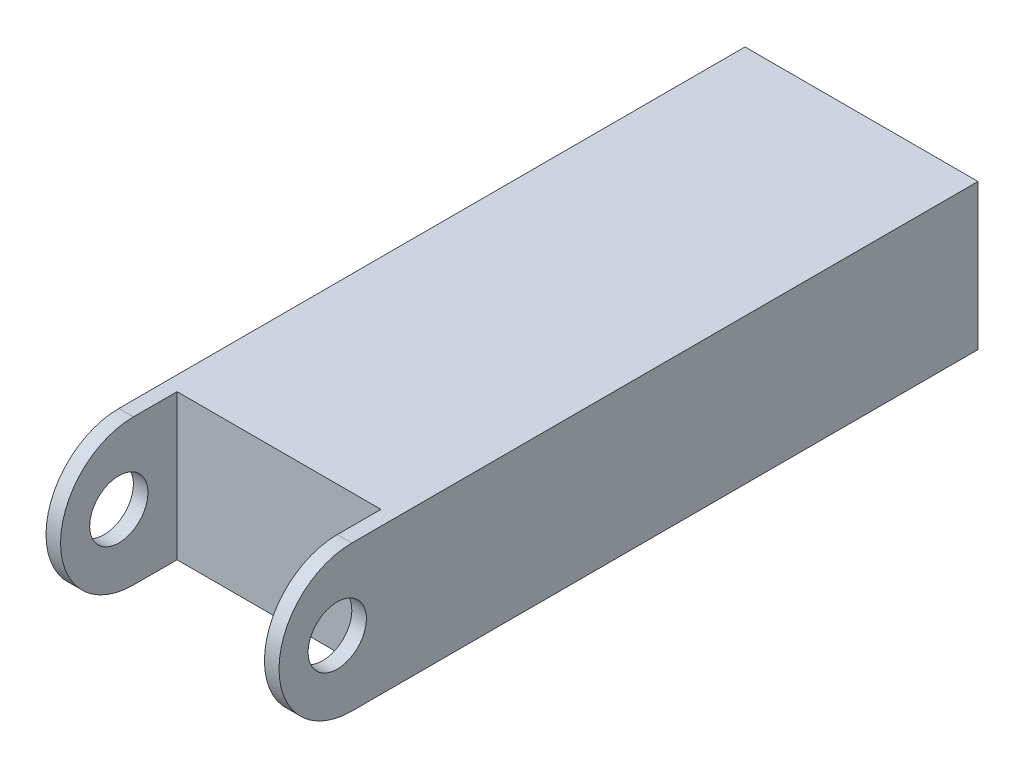
SolidWorks part; units mm, degrees
material "Mahogany"
ref_plane "Front Plane" through (0, 0, 0) normal (0, 0, 1) x (1, 0, 0)
ref_plane "Top Plane" through (0, 0, 0) normal (0, 1, 0) x (1, 0, 0)
ref_plane "Right Plane" through (0, 0, 0) normal (1, 0, 0) x (0, 0, -1)
sketch "Sketch1" plane through (0, 0, 0) normal (0, 0, 1) x (1, 0, 0)
  line L1 (-40, 25) -> (40, 25)
  line L2 (-40, 25) -> (-40, -25)
  line L3 (-40, -25) -> (40, -25)
  line L4 (40, 25) -> (40, -25)
  line L5 (-40, 25) -> (40, -25) construction
  line L6 (-40, -25) -> (40, 25) construction
  point P0 (0, 0)
  dimension "D1" = 80
  dimension "D2" = 50
extrude "Boss-Extrude1" add sketch "Sketch1" against normal blind 200
ref_plane "Plane1" through (0, 0, -200) normal (0, 0, -1) x (-1, 0, 0)
ref_plane "Plane2" through (40, 0, 0) normal (1, 0, 0) x (0, 0, -1)
sketch "Sketch4" plane through (40, 0, 0) normal (1, 0, 0) x (0, 0, -1)
  line L0 (0, 25) -> (0, -25)
  line L1 (0, -25) -> (-40, -25)
  line L2 (-40, -25) -> (-40, 25)
  line L3 (-40, 25) -> (0, 25)
  circle A0 centre (-20, 0) radius 10
  dimension "D2" = 20
  dimension "D1" = 40
  dimension "D3" = 20
  dimension "D4" = 25
extrude "Boss-Extrude3" add sketch "Sketch4" against normal blind 5
fillet "Fillet1" 2 edges at (37.5, -25, 40) (37.5, 25, 40) type full round first side face at (11.6667, -25, -53.3333) second side face at (11.6667, 25, -53.3333) middle face at (37.5, 0, 40)
mirror "Mirror1" about plane through (0, 0, 0) normal (1, 0, 0) of "Fillet1", "Boss-Extrude3"
